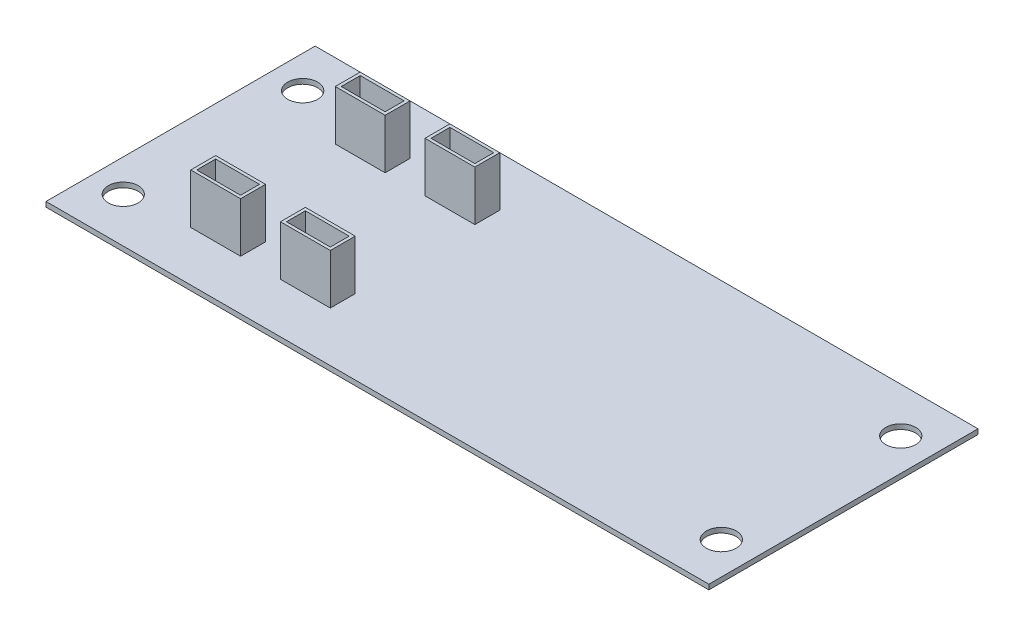
SolidWorks part; units mm, degrees
ref_plane "Front Plane" through (0, 0, 0) normal (0, 0, 1) x (1, 0, 0)
ref_plane "Top Plane" through (0, 0, 0) normal (0, 1, 0) x (1, 0, 0)
ref_plane "Right Plane" through (0, 0, 0) normal (1, 0, 0) x (0, 0, -1)
sketch "Sketch1" plane through (0, 0, 0) normal (0, 1, 0) x (1, 0, 0)
  line L1 (-33.25, 13.5) -> (33.25, 13.5)
  line L2 (-33.25, 13.5) -> (-33.25, -13.5)
  line L3 (-33.25, -13.5) -> (33.25, -13.5)
  line L4 (33.25, 13.5) -> (33.25, -13.5)
  line L5 (-33.25, 13.5) -> (33.25, -13.5) construction
  line L6 (-33.25, -13.5) -> (33.25, 13.5) construction
  circle A0 centre (-30, 9) radius 1.5
  circle A1 centre (-30, -9) radius 1.5
  circle A2 centre (30, 9) radius 1.5
  circle A3 centre (30, -9) radius 1.5
  point P0 (0, 0)
  point P14 (0, 0)
  point P15 (0, 0)
  point P16 (0, 0)
  point P17 (0, 0)
  dimension "D7" = 3
  dimension "D8" = 3
  dimension "D9" = 3
  dimension "D10" = 3
  dimension "D1" = 27
  dimension "D2" = 66.5
  dimension "D3" = 18
  dimension "D4" = 3.25
  dimension "D5" = 60
  dimension "D6" = 4.5
extrude "Boss-Extrude1" add sketch "Sketch1" along normal blind 0.5
sketch "Sketch2" plane through (0, 0.5, 0) normal (0, 1, 0) x (1, 0, 0)
  line L0 (33.25, 13.5) -> (-33.25, 13.5) construction
  line L1 (-23.7289, 6) -> (-9.7289, 6) construction
  line L2 (-23.7289, 6) -> (-23.7289, -6) construction
  line L3 (-23.7289, -6) -> (-9.7289, -6) construction
  line L4 (-9.7289, 6) -> (-9.7289, -6) construction
  line L6 (-23.7289, 6) -> (-23.7289, 8.5)
  line L7 (-23.7289, 8.5) -> (-18.7289, 8.5)
  line L8 (-18.7289, 8.5) -> (-18.7289, 6)
  line L9 (-18.7289, 6) -> (-23.7289, 6)
  line L10 (-23.4289, 8.2) -> (-19.0289, 8.2)
  line L11 (-19.0289, 8.2) -> (-19.0289, 6.3)
  line L12 (-19.0289, 6.3) -> (-23.4289, 6.3)
  line L13 (-23.4289, 6.3) -> (-23.4289, 8.2)
  line L14 (-16.7289, 6) -> (-16.7289, -6) construction
  line L15 (-14.4289, 6.3) -> (-10.0289, 6.3)
  line L16 (-10.0289, 8.2) -> (-14.4289, 8.2)
  line L17 (-9.7289, 8.5) -> (-14.7289, 8.5)
  line L18 (-14.7289, 6) -> (-9.7289, 6)
  line L19 (-9.7289, 6) -> (-9.7289, 8.5)
  line L20 (-10.0289, 6.3) -> (-10.0289, 8.2)
  line L21 (-14.4289, 8.2) -> (-14.4289, 6.3)
  line L22 (-14.7289, 8.5) -> (-14.7289, 6)
  line L23 (-23.7289, 0) -> (-9.7289, 0) construction
  line L24 (-23.7289, -6) -> (-9.7289, -6) construction
  line L25 (-14.7289, -8.5) -> (-14.7289, -6)
  line L26 (-14.4289, -8.2) -> (-14.4289, -6.3)
  line L27 (-10.0289, -6.3) -> (-10.0289, -8.2)
  line L28 (-9.7289, -6) -> (-9.7289, -8.5)
  line L29 (-14.7289, -6) -> (-9.7289, -6)
  line L30 (-9.7289, -8.5) -> (-14.7289, -8.5)
  line L31 (-10.0289, -8.2) -> (-14.4289, -8.2)
  line L32 (-14.4289, -6.3) -> (-10.0289, -6.3)
  line L33 (-23.4289, -6.3) -> (-23.4289, -8.2)
  line L34 (-19.0289, -6.3) -> (-23.4289, -6.3)
  line L35 (-19.0289, -8.2) -> (-19.0289, -6.3)
  line L36 (-23.4289, -8.2) -> (-19.0289, -8.2)
  line L37 (-18.7289, -6) -> (-23.7289, -6)
  line L38 (-18.7289, -8.5) -> (-18.7289, -6)
  line L39 (-23.7289, -8.5) -> (-18.7289, -8.5)
  line L40 (-23.7289, -6) -> (-23.7289, -8.5)
  point P0 (-9.7289, 0)
  dimension "D1" = 14
  dimension "D2" = 12
  dimension "D3" = 13.5
  dimension "D4" = 2.5
  dimension "D5" = 5
  dimension "D6" = 0.3
extrude "Boss-Extrude2" add sketch "Sketch2" along normal blind 5
